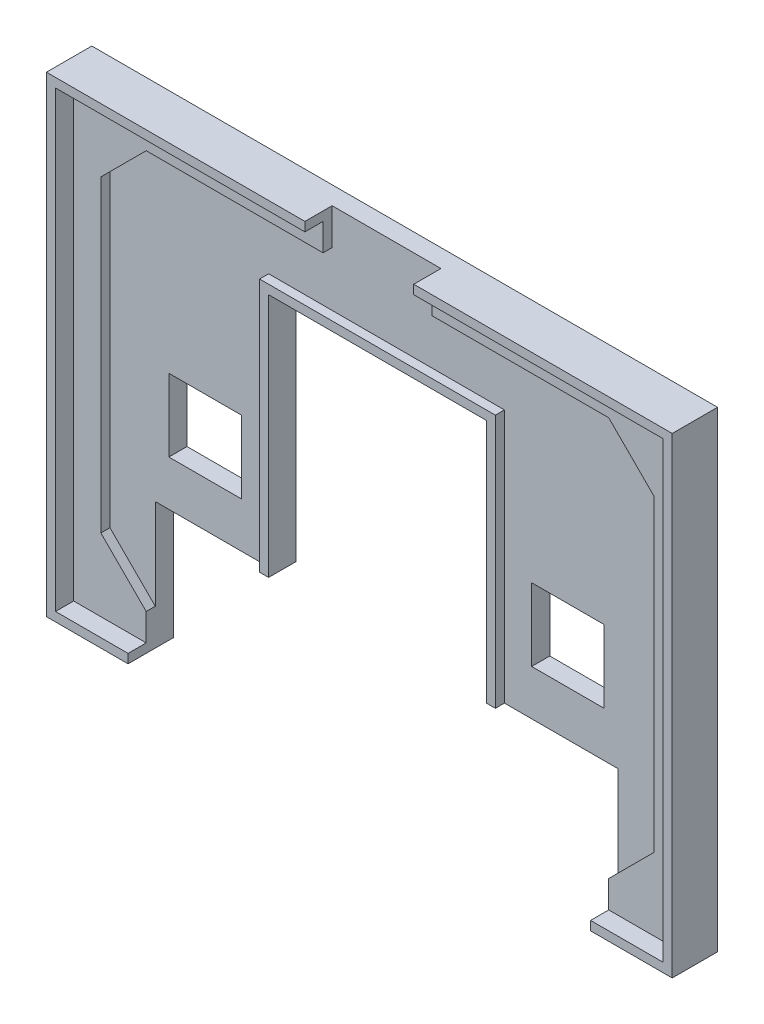
SolidWorks part; units mm, degrees
ref_plane "Přední rovina" through (0, 0, 0) normal (0, 0, 1) x (1, 0, 0)
ref_plane "Horní rovina" through (0, 0, 0) normal (0, 1, 0) x (1, 0, 0)
ref_plane "Pravá rovina" through (0, 0, 0) normal (1, 0, 0) x (0, 0, -1)
sketch "Skica1" plane through (0, 0, 0) normal (0, 0, 1) x (1, 0, 0)
  line L1 (-33.5, -25) -> (33.5, -25)
  line L2 (-33.5, -25) -> (-33.5, 25)
  line L3 (-33.5, 25) -> (33.5, 25)
  line L4 (33.5, -25) -> (33.5, 25)
  line L5 (-33.5, -25) -> (33.5, 25) construction
  line L6 (-33.5, 25) -> (33.5, -25) construction
  point P0 (0, 0)
  dimension "D1" = 67
  dimension "D2" = 50
extrude "Přidat vysunutím1" add sketch "Skica1" along normal blind 3
sketch "Skica2" plane through (0, 0, 3) normal (0, 0, 1) x (1, 0, 0)
  line L0 (-1000, 0) -> (49000, 0) construction
  line L1 (0, -1000) -> (0, 49000) construction
  line L2 (-1000, -22) -> (49000, -22) construction
  line L3 (-25.5, -1000) -> (-25.5, 49000) construction
  line L4 (-30.5, -1000) -> (-30.5, 49000) construction
  line L6 (-33.5, -25) -> (33.5, -25) construction
  line L7 (-25.5, -22) -> (-30.5, -17)
  line L8 (-30.5, -17) -> (-30.5, 17)
  line L9 (-25.5, -22) -> (25.5, -22)
  line L10 (30.5, -17) -> (30.5, 17)
  line L11 (25.5, -22) -> (30.5, -17)
  line L12 (25.5, 22) -> (30.5, 17)
  line L13 (-25.5, 22) -> (25.5, 22)
  line L14 (-25.5, 22) -> (-30.5, 17)
  point P20 (0, -22)
  point P21 (30.5, 0)
  point P24 (-30.5, 0)
  dimension "D1" = 30.5
  dimension "D2" = 5
  dimension "D3" = 3
  dimension "D4" = 45
extrude "Odebrat vysunutím1" cut sketch "Skica2" against normal offset from surface (1 mm away) 2 up to face at (0, 0, 0)
sketch "Skica3" plane through (0, 0, 0) normal (0, 0, -1) x (-1, 0, 0)
  line L0 (0, -1000) -> (0, 49000) construction
  line L1 (33.5, -25) -> (-33.5, -25) construction
  line L2 (24, 1) -> (16, 1)
  line L3 (24, 1) -> (24, -7)
  line L4 (24, -7) -> (16, -7)
  line L5 (16, 1) -> (16, -7)
  line L6 (-16, 1) -> (-16, -7)
  line L7 (33.5, -25) -> (-33.5, -25) construction
  line L8 (25.5, -25) -> (-25.5, -25)
  line L9 (25.5, -25) -> (25.5, -12)
  line L11 (-25.5, -25) -> (-25.5, -12)
  line L12 (-24, -7) -> (-16, -7)
  line L13 (25.5, -12) -> (12, -12)
  line L15 (12, -12) -> (12, 15)
  line L16 (12, 15) -> (-12, 15)
  line L17 (-12, -12) -> (-12, 15)
  line L18 (-12, -12) -> (-25.5, -12)
  line L19 (-24, 1) -> (-24, -7)
  line L20 (-24, 1) -> (-16, 1)
  dimension "D1" = 16
  dimension "D2" = 8
  dimension "D3" = 18
  dimension "D4" = 13
  dimension "D5" = 51
  dimension "D6" = 24
  dimension "D7" = 27
extrude "Odebrat vysunutím2" cut sketch "Skica3" against normal through all
sketch "Skica4" plane through (0, 0, 2) normal (0, 0, 1) x (1, 0, 0)
  line L0 (12, 15) -> (12, -12) construction
  line L1 (-12, -12) -> (-12, 15) construction
  line L2 (-12, 15) -> (12, 15) construction
  line L3 (12, 15) -> (12, -12)
  line L4 (-12, -12) -> (-12, 15)
  line L5 (-12, 15) -> (12, 15)
extrude "Vysunout tenkostěnný1" add sketch "Skica4" along normal up to surface (1 mm away) thin up to face at (0, -3.5714, 3) thin type one direction reverse wall 1
sketch "Skica5" plane through (0, 0, 0) normal (0, 0, -1) x (-1, 0, 0)
  line L0 (-33.5, 25) -> (33.5, 25) construction
  line L1 (33.5, 25) -> (33.5, -25) construction
  line L2 (33.5, -25) -> (25.5, -25) construction
  line L3 (-33.5, -25) -> (-33.5, 25) construction
  line L4 (-25.5, -25) -> (-33.5, -25) construction
  line L5 (-33.5, 25) -> (33.5, 25)
  line L6 (33.5, 25) -> (33.5, -25)
  line L7 (33.5, -25) -> (25.5, -25)
  line L8 (-33.5, -25) -> (-33.5, 25)
  line L9 (-25.5, -25) -> (-33.5, -25)
extrude "Vysunout tenkostěnný2" add sketch "Skica5" against normal blind 5 thin thin type one direction reverse wall 1
sketch "Skica6" plane through (0, 0, 2) normal (0, 0, 1) x (1, 0, 0)
  line L0 (0, -1000) -> (0, 49000) construction
  line L1 (25.5, 22) -> (-25.5, 22) construction
  line L2 (-6, 22) -> (6, 22)
  line L3 (-6, 22) -> (-6, 26)
  line L4 (-6, 26) -> (6, 26)
  line L5 (6, 22) -> (6, 26)
  line L6 (34.5, 26) -> (-34.5, 26) construction
  dimension "D1" = 12
extrude "Odebrat vysunutím3" cut sketch "Skica6" along normal through all
sketch "Skica7" plane through (0, 0, 0) normal (0, 0, -1) x (-1, 0, 0)
  line L0 (-12, 15) -> (-12, -12) construction
  line L1 (-30.5, 21) -> (-25.5, 21)
  line L2 (-30.5, 21) -> (-30.5, 16)
  line L3 (-30.5, 16) -> (-25.5, 16)
  line L4 (-25.5, 21) -> (-25.5, 16)
  line L5 (-21, 21) -> (-16, 21)
  line L6 (-21, 21) -> (-21, 16)
  line L7 (-21, 16) -> (-16, 16)
  line L8 (-16, 21) -> (-16, 16)
  line L9 (-34.5, -26) -> (-34.5, 26) construction
  line L10 (-34.5, 26) -> (34.5, 26) construction
  line L11 (-25.5, 15.99) -> (-25.5, 13.5)
  line L12 (-25.5, 13.5) -> (-28, 13.5)
  line L13 (-28, 13.5) -> (-28, 6)
  line L14 (-28, 6) -> (-25.5, 6)
  line L15 (-25.5, 6) -> (-25.5, 8.49)
  line L16 (-25.5, 8.49) -> (-21, 8.49)
  line L17 (-21, 8.49) -> (-21, 6)
  line L18 (-21, 6) -> (-18.5, 6)
  line L19 (-18.5, 6) -> (-18.5, 13.5)
  line L20 (-18.5, 13.5) -> (-21, 13.5)
  line L21 (-21, 13.5) -> (-21, 15.99)
  line L22 (-21, 15.99) -> (-25.5, 15.99)
  line L23 (34.5, 26) -> (34.5, -26) construction
  line L24 (34.5, -26) -> (25.5, -26) construction
  line L25 (21, 13.5) -> (18.5, 13.5)
  line L26 (12, -12) -> (12, 15) construction
  line L27 (16, 21) -> (21, 21)
  line L28 (16, 21) -> (16, 16)
  line L29 (16, 16) -> (21, 16)
  line L30 (21, 21) -> (21, 16)
  line L31 (25.5, 21) -> (30.5, 21)
  line L32 (25.5, 21) -> (25.5, 16)
  line L33 (25.5, 16) -> (30.5, 16)
  line L34 (30.5, 21) -> (30.5, 16)
  line L35 (18.5, 13.5) -> (18.5, 6)
  line L36 (18.5, 6) -> (21, 6)
  line L37 (21, 6) -> (21, 8.49)
  line L38 (21, 8.49) -> (25.5, 8.49)
  line L39 (25.5, 8.49) -> (25.5, 6)
  line L40 (25.5, 6) -> (28, 6)
  line L41 (28, 6) -> (28, 13.5)
  line L42 (28, 13.5) -> (25.5, 13.5)
  line L43 (25.5, 13.5) -> (25.5, 15.99)
  line L44 (25.5, 15.99) -> (21, 15.99)
  line L45 (21, 15.99) -> (21, 13.5)
  line L46 (-11.2, 23.3) -> (-11.2, 17.7)
  line L47 (-11.2, 17.7) -> (-7.2, 17.7)
  line L48 (-7.2, 17.7) -> (-7.2, 18.5)
  line L49 (-7.2, 18.5) -> (-6.4, 18.5)
  line L50 (-6.4, 18.5) -> (-6.4, 20.1)
  line L51 (-6.4, 20.1) -> (-7.2, 20.1)
  line L52 (-7.2, 20.1) -> (-7.2, 20.9)
  line L53 (-7.2, 20.9) -> (-6.4, 20.9)
  line L54 (-6.4, 20.9) -> (-6.4, 22.5)
  line L55 (-6.4, 22.5) -> (-7.2, 22.5)
  line L56 (-7.2, 22.5) -> (-7.2, 23.3)
  line L57 (-7.2, 23.3) -> (-11.2, 23.3)
  line L58 (-1.6, 23.3) -> (-4.8, 23.3)
  line L59 (-4.8, 23.3) -> (-4.8, 22.5)
  line L60 (-4.8, 22.5) -> (-5.6, 22.5)
  line L61 (-5.6, 22.5) -> (-5.6, 18.5)
  line L62 (-5.6, 18.5) -> (-4.8, 18.5)
  line L63 (-4.8, 18.5) -> (-4.8, 17.7)
  line L64 (-4.8, 17.7) -> (-1.6, 17.7)
  line L65 (-1.6, 17.7) -> (-1.6, 18.5)
  line L66 (-1.6, 18.5) -> (-0.8, 18.5)
  line L67 (-0.8, 18.5) -> (-0.8, 22.5)
  line L68 (-0.8, 22.5) -> (-1.6, 22.5)
  line L69 (-1.6, 22.5) -> (-1.6, 23.3)
  line L70 (0.8, 23.3) -> (0.8, 22.5)
  line L71 (0.8, 22.5) -> (0, 22.5)
  line L72 (0, 22.5) -> (0, 18.5)
  line L73 (0, 18.5) -> (0.8, 18.5)
  line L74 (0.8, 18.5) -> (0.8, 17.7)
  line L75 (0.8, 17.7) -> (4, 17.7)
  line L76 (4, 17.7) -> (4, 18.5)
  line L77 (4, 18.5) -> (4.8, 18.5)
  line L78 (4.8, 18.5) -> (4.8, 22.5)
  line L79 (4.8, 22.5) -> (4, 22.5)
  line L80 (4, 22.5) -> (4, 23.3)
  line L81 (4, 23.3) -> (0.8, 23.3)
  line L82 (-25.5, -26) -> (-34.5, -26) construction
  line L83 (12, 15) -> (-12, 15) construction
  line L84 (5.6, 17.7) -> (5.6, 23.3)
  line L85 (5.6, 23.3) -> (7.2, 23.3)
  line L86 (7.2, 23.3) -> (7.2, 22.5)
  line L87 (7.2, 22.5) -> (8, 22.5)
  line L88 (8, 22.5) -> (8, 21.7)
  line L89 (8, 21.7) -> (8.8, 21.7)
  line L90 (8.8, 21.7) -> (8.8, 22.5)
  line L91 (8.8, 22.5) -> (9.6, 22.5)
  line L92 (9.6, 22.5) -> (9.6, 23.3)
  line L93 (9.6, 23.3) -> (11.2, 23.3)
  line L94 (11.2, 23.3) -> (11.2, 17.7)
  line L95 (11.2, 17.7) -> (9.6, 17.7)
  line L96 (9.6, 17.7) -> (9.6, 19.3)
  line L97 (9.6, 19.3) -> (8.8, 19.3)
  line L98 (8.8, 19.3) -> (8.8, 18.5)
  line L99 (8.8, 18.5) -> (8, 18.5)
  line L100 (8, 18.5) -> (8, 19.3)
  line L101 (8, 19.3) -> (7.2, 19.3)
  line L102 (7.2, 19.3) -> (7.2, 17.7)
  line L103 (7.2, 17.7) -> (5.6, 17.7)
  dimension "D1" = 5
  dimension "D2" = 5
  dimension "D3" = 5
  dimension "D4" = 5
  dimension "D5" = 4
  dimension "D6" = 4
  dimension "D7" = 5
  dimension "D8" = 5
  dimension "D9" = 7.5
  dimension "D10" = 7.5
  dimension "D11" = 2.5
  dimension "D12" = 2.5
  dimension "D13" = 2.5
  dimension "D14" = 2.5
  dimension "D15" = 0
  dimension "D16" = 0.01
  dimension "D17" = 2.5
  dimension "D18" = 2.5
  dimension "D19" = 7.5
  dimension "D20" = 5
  dimension "D21" = 5
  dimension "D22" = 5
  dimension "D23" = 5
  dimension "D24" = 4
  dimension "D25" = 4
  dimension "D26" = 5
  dimension "D27" = 5
  dimension "D28" = 2.5
  dimension "D29" = 2.5
  dimension "D30" = 7.5
  dimension "D31" = 7.5
  dimension "D32" = 0.01
  dimension "D33" = 7.5
  dimension "D34" = 2.5
  dimension "D35" = 2.5
  dimension "D36" = 4.5
  dimension "D37" = 2.5
  dimension "D38" = 2.5
  dimension "D39" = 5.6
  dimension "D40" = 2.7
  dimension "D41" = 0.8
  dimension "D42" = 0.8
  dimension "D43" = 1.6
  dimension "D44" = 0.8
  dimension "D45" = 1.6
  dimension "D46" = 4
  dimension "D47" = 4
  dimension "D48" = 0.8
  dimension "D49" = 0.8
  dimension "D50" = 0.8
  dimension "D51" = 3.2
  dimension "D52" = 0.8
  dimension "D53" = 3.2
  dimension "D54" = 0.8
  dimension "D55" = 0.8
  dimension "D56" = 0.8
  dimension "D57" = 0.8
  dimension "D58" = 0.8
  dimension "D59" = 0.8
  dimension "D60" = 0.8
  dimension "D61" = 4
  dimension "D62" = 3.2
  dimension "D63" = 0.8
  dimension "D64" = 0.8
  dimension "D65" = 0.8
  dimension "D66" = 3.2
  dimension "D67" = 4
  dimension "D68" = 4
  dimension "D69" = 0.8
  dimension "D70" = 0.8
  dimension "D71" = 0.8
  dimension "D72" = 0.8
  dimension "D73" = 2.7
  dimension "D74" = 1.6
  dimension "D75" = 1.6
  dimension "D76" = 1.6
  dimension "D77" = 1.6
  dimension "D78" = 0.8
  dimension "D79" = 0.8
  dimension "D80" = 0.8
  dimension "D81" = 0.8
  dimension "D82" = 0.8
  dimension "D83" = 0.8
  dimension "D84" = 2.7
  dimension "D85" = 0.8
  dimension "D86" = 0.8
  dimension "D87" = 0.8
  dimension "D88" = 0.8
  dimension "D89" = 0.8
  dimension "D90" = 0.8
  dimension "D91" = 2.7
  dimension "D92" = 1.6
  dimension "D93" = 1.6
extrude "Odebrat vysunutím5" cut sketch "Skica7" against normal blind 1
sketch "Skica8" plane through (0, 0, 0) normal (0, 0, -1) x (-1, 0, 0)
  line L0 (-11.2, 23.3) -> (-11.2, 17.7) construction
  line L1 (-9.6, 21.7) -> (-8, 21.7)
  line L2 (-9.6, 21.7) -> (-9.6, 20.9)
  line L3 (-9.6, 20.9) -> (-8, 20.9)
  line L4 (-8, 21.7) -> (-8, 20.9)
  line L5 (-7.2, 23.3) -> (-11.2, 23.3) construction
  line L6 (-1.6, 23.3) -> (-4.8, 23.3) construction
  line L7 (-11.2, 17.7) -> (-7.2, 17.7) construction
  line L8 (-9.6, 20.1) -> (-8, 20.1)
  line L9 (-9.6, 20.1) -> (-9.6, 19.3)
  line L10 (-9.6, 19.3) -> (-8, 19.3)
  line L11 (-8, 20.1) -> (-8, 19.3)
  line L12 (-11.2, 23.3) -> (-11.2, 17.7) construction
  line L13 (-4, 21.7) -> (-2.4, 21.7)
  line L14 (-4, 21.7) -> (-4, 19.3)
  line L15 (-4, 19.3) -> (-2.4, 19.3)
  line L16 (-2.4, 21.7) -> (-2.4, 19.3)
  line L17 (-4.8, 17.7) -> (-1.6, 17.7) construction
  line L18 (-0.8, 18.5) -> (-0.8, 22.5) construction
  line L19 (-5.6, 22.5) -> (-5.6, 18.5) construction
  line L20 (4, 23.3) -> (0.8, 23.3) construction
  line L21 (1.6, 21.7) -> (3.2, 21.7)
  line L22 (1.6, 21.7) -> (1.6, 19.3)
  line L23 (1.6, 19.3) -> (3.2, 19.3)
  line L24 (3.2, 21.7) -> (3.2, 19.3)
  line L25 (4.8, 18.5) -> (4.8, 22.5) construction
  line L26 (0.8, 17.7) -> (4, 17.7) construction
  line L27 (0, 22.5) -> (0, 18.5) construction
  dimension "D1" = 0.8
  dimension "D2" = 1.6
  dimension "D3" = 1.6
  dimension "D4" = 1.6
  dimension "D5" = 0.8
  dimension "D6" = 1.6
  dimension "D7" = 1.6
  dimension "D8" = 1.6
  dimension "D9" = 1.6
  dimension "D10" = 1.6
  dimension "D11" = 1.6
  dimension "D12" = 1.6
  dimension "D13" = 1.6
  dimension "D14" = 1.6
  dimension "D15" = 1.6
  dimension "D16" = 1.6
extrude "Přidat vysunutím3" add sketch "Skica8" along normal blind 1 from offset 1 offset against normal yes
